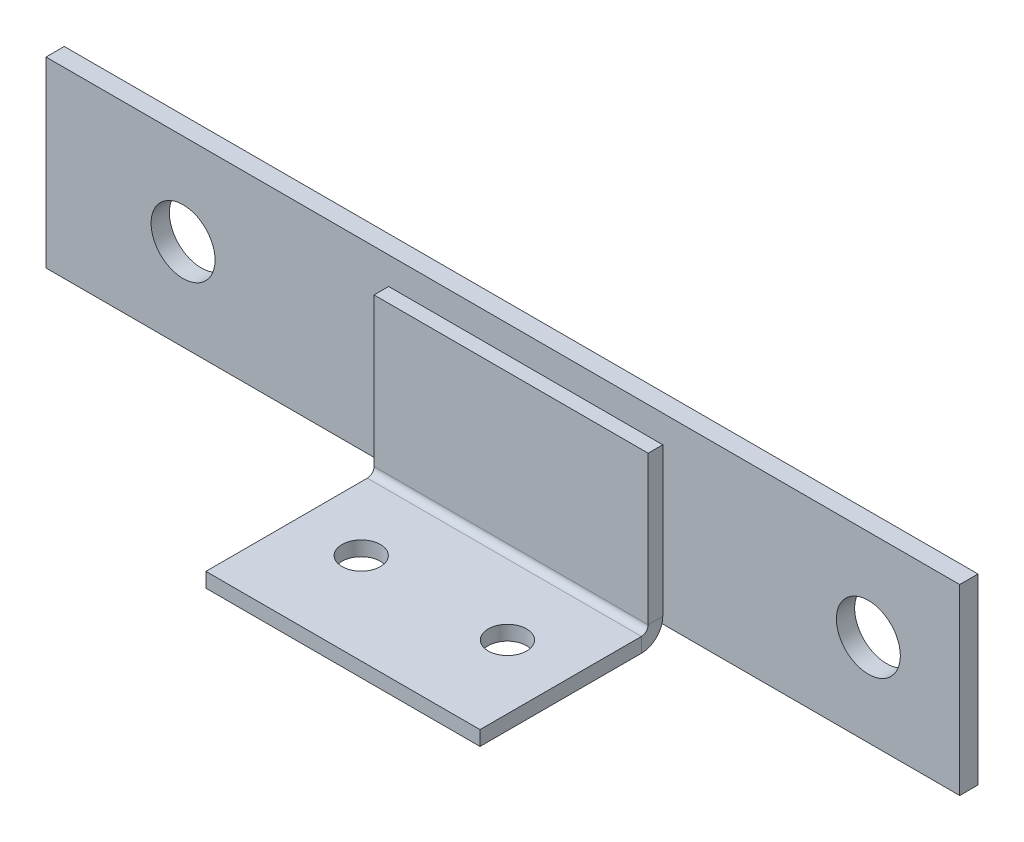
SolidWorks part; units mm, degrees
note: The reader was unsure of these and kept them because the rebuilt part matched: flange length of "边线-法兰1".
ref_plane "前视基准面" through (0, 0, 0) normal (0, 0, 1) x (1, 0, 0)
ref_plane "上视基准面" through (0, 0, 0) normal (0, 1, 0) x (1, 0, 0)
ref_plane "右视基准面" through (0, 0, 0) normal (1, 0, 0) x (0, 0, -1)
sketch "草图1" plane through (0, 0, 0) normal (0, 0, 1) x (1, 0, 0)
  line L1 (47.5, -7.5) -> (-52.5, -7.5)
  line L2 (47.5, -7.5) -> (47.5, 12.5)
  line L3 (47.5, 12.5) -> (-52.5, 12.5)
  line L4 (-52.5, -7.5) -> (-52.5, 12.5)
  point P0 (0, 0)
  dimension "D1" = 20
  dimension "D2" = 100
extrude "凸台-拉伸1" add sketch "草图1" along normal blind 2
sketch "草图2" plane through (0, 0, 2) normal (0, 0, 1) x (1, 0, 0)
  line L1 (0, 23.1328) -> (0, -30.0825) construction
  line L2 (-52.5, -7.5) -> (47.5, -7.5) construction
  line L3 (-15, -7.5) -> (15, -7.5)
  line L4 (-15, -7.5) -> (-15, 9.5)
  line L5 (-15, 9.5) -> (15, 9.5)
  line L6 (15, -7.5) -> (15, 9.5)
  dimension "D1" = 30
  dimension "D2" = 17
sheet metal parameters "钣金1" thickness 1.6 parameters "D1"=0.7366
base flange "基体-法兰1" sketch "草图2" thickness 1.6 reverse thickness direction yes parameters "D1"=0.7366
sketch "草图11" plane through (0, 0, 2) normal (0, 0, 1) x (1, 0, 0)
  line L0 (0, 34.7183) -> (0, -24.9081) construction
  line L1 (47.5, 12.5) -> (-52.5, 12.5) construction
  circle A0 centre (-37.5, 2.5) radius 3.5
  circle A1 centre (37.5, 2.5) radius 3.5
  dimension "D1" = 7
  dimension "D2" = 7
  dimension "D3" = 37.5
  dimension "D4" = 37.5
  dimension "D5" = 10
  dimension "D6" = 10
extrude "切除-拉伸2" cut sketch "草图11" against normal through all normal cut yes
edge flange "边线-法兰1" sketch "草图14" flange angle 90 flange length 20 flange position material outside bend radius 0.7366 thickness 1.6 relief rectangular parameters "D6"=10
sketch "草图14" plane through (0, -7.5, 3.6) normal (0, -1, 0) x (1, 0, 0)
  line L2 (-15, 0) -> (-15, 18.4)
  line L3 (-15, 18.4) -> (15, 18.4)
  line L4 (15, 18.4) -> (15, 0)
  line L5 (-15, 0) -> (15, 0) construction
  line L6 (-15, 0) -> (15, 0)
bend "边线折弯1" bend radius 0.7366 bend angle 90 parameters "D5"=1
sketch "草图15" plane through (0, -7.5, 0) normal (0, 1, 0) x (1, 0, 0)
  line L0 (0, 4.1197) -> (0, -30.4029) construction
  line L1 (15, -22) -> (-15, -22) construction
  circle A0 centre (-8, -12) radius 2.1
  circle A1 centre (8, -12) radius 2.1
  dimension "D1" = 4.2
  dimension "D2" = 4.2
  dimension "D3" = 8
  dimension "D4" = 8
  dimension "D5" = 10
  dimension "D6" = 10
extrude "切除-拉伸3" cut sketch "草图15" against normal blind 10 normal cut yes
flat pattern "平板型式1" [suppressed]
sketch "折弯-线1" plane through (0, 0, 0) normal (0, 1, 0) x (-1, 0, 0)
sketch3d "边界框1" [suppressed]
  line L0 (0, -17, 0) -> (-30, -17, 0) construction
  line L1 (0, 0, 0) -> (-30, 0, 0) construction
  line L2 (0, -17, 0) -> (0, 0, 0) construction
  line L3 (-30, -17, 0) -> (-30, 0, 0) construction
bend of the flat pattern "展开-<边线折弯1>1"
